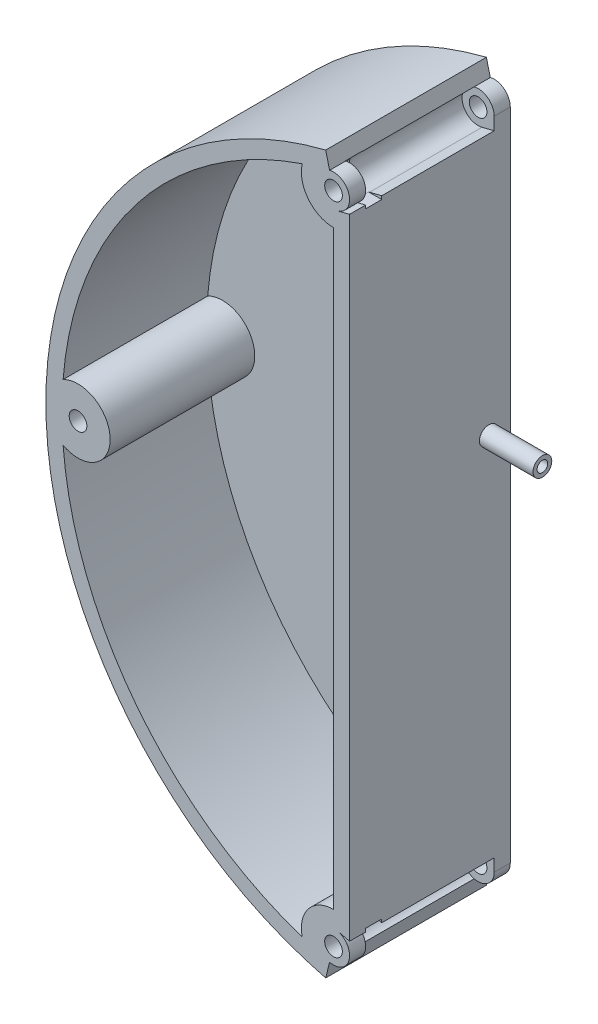
SolidWorks part; units mm, degrees
ref_plane "Front Plane" through (0, 0, 0) normal (0, 0, 1) x (1, 0, 0)
ref_plane "Top Plane" through (0, 0, 0) normal (0, 1, 0) x (1, 0, 0)
ref_plane "Right Plane" through (0, 0, 0) normal (1, 0, 0) x (0, 0, -1)
sketch "Sketch1" plane through (0, 0, 0) normal (0, 0, 1) x (1, 0, 0)
  line L0 (-12.3, -61.1139) -> (-12.3, 61.1139)
  line L1 (-12, -28.4) -> (-12, -52) construction
  line L2 (-16.7571, 66.9343) -> (-16.0286, 64.0241)
  line L4 (-16.7571, -66.9343) -> (-16.0286, -64.0241)
  line L5 (-63, 0) -> (0, 0) construction
  arc A1 (-16.0286, -64.0241) -> (-12.3, -61.1139) centre (-15.3, -61.1139) cw
  circle A2 centre (0, 0) radius 69 construction
  arc A3 (-16.0286, 64.0241) -> (-12.3, 61.1139) centre (-15.3, 61.1139) ccw
  circle A4 centre (-63, 0) radius 3
  arc A6 (-16.7571, 66.9343) -> (-16.7571, -66.9343) centre (0, 0) ccw
  dimension "D2" = 3
  dimension "D6" = 3
  dimension "D8" = 6
  dimension "D1" = 0.3
  dimension "D3" = 3
  dimension "D5" = 3
  dimension "D9" = 63
extrude "Boss-Extrude2" add sketch "Sketch1" along normal blind 30
shell "Shell1" thickness 3 removed face at (-24.7296, 0, 30)
sketch "Sketch3" plane through (-12.3, 0, 0) normal (1, 0, 0) x (0, 1, 0)
  line L0 (-61.1139, 0) -> (61.1139, 0) construction
  circle A0 centre (10, 4) radius 1.75
  dimension "D1" = 3.5
  dimension "D2" = 4
  dimension "D3" = 10
extrude "Boss-Extrude3" add sketch "Sketch3" along normal blind 10
sketch "Sketch5" plane through (0, 0, 0) normal (0, 0, 1) x (1, 0, 0)
  line L0 (-12.3, -61.1139) -> (-12.3, 61.1139)
  line L2 (-16.7571, 66.9343) -> (-16.0286, 64.0241)
  line L4 (-16.7571, -66.9343) -> (-16.0286, -64.0241)
  line L5 (-63, 0) -> (0, 0) construction
  circle A4 centre (-63, 0) radius 1.65
  circle A5 centre (-15.3, 61.1139) radius 1.65
  arc A6 (-16.7571, 66.9343) -> (-16.7571, -66.9343) centre (0, 0) ccw
  arc A7 (-16.0286, 64.0241) -> (-12.3, 61.1139) centre (-15.3, 61.1139) cw
  circle A8 centre (-15.3, -61.1139) radius 1.65
  arc A9 (-12.3, -61.1139) -> (-16.0286, -64.0241) centre (-15.3, -61.1139) cw
  dimension "D2" = 3.3
  dimension "D8" = 3.3
  dimension "D1" = 3.3
  dimension "D3" = 3
  dimension "D5" = 3
extrude "Boss-Extrude4" add sketch "Sketch5" along normal blind 3 contours A4 L0 A7 L2 A6 L4 A9 A8 A5 region at (-36.1775, 0, 0)
sketch "Sketch6" plane through (0, 0, 30) normal (0, 0, 1) x (1, 0, 0)
  line L0 (-63, 3) -> (-68.9348, 3)
  line L1 (-63, -3) -> (-68.9348, -3)
  line L2 (-16.0286, -64.0241) -> (-14.5714, -58.2037) construction
  line L3 (-14.5714, -58.2037) -> (-12.3, -58.7724)
  line L4 (-12.3, -61.1139) -> (-12.3, 61.1139) construction
  line L5 (-12.3, -58.7724) -> (-12.3, -61.1139)
  line L6 (-16.0286, 64.0241) -> (-14.5714, 58.2037) construction
  line L7 (-14.5714, 58.2037) -> (-12.3, 58.7724)
  line L8 (-12.3, 58.7724) -> (-12.3, 61.1139)
  arc A1 (-63, -3) -> (-63, 3) centre (-63, 0) ccw
  arc A2 (-12.3, -61.1139) -> (-14.5714, -58.2037) centre (-15.3, -61.1139) ccw
  arc A3 (-14.5714, 58.2037) -> (-12.3, 61.1139) centre (-15.3, 61.1139) ccw
  arc A4 (-16.7571, 66.9343) -> (-16.7571, -66.9343) centre (0, 0) ccw construction
  arc A5 (-68.9348, 3) -> (-68.9348, -3) centre (-68.9348, 0) ccw
  arc A6 (-12.3, -61.1139) -> (-16.0286, -64.0241) centre (-15.3, -61.1139) ccw construction
  arc A7 (-16.0286, 64.0241) -> (-12.3, 61.1139) centre (-15.3, 61.1139) ccw construction
extrude "Cut-Extrude1" cut sketch "Sketch6" against normal up to surface (27 mm away) up to face at (-61.35, 0, 3)
sketch "Sketch7" plane through (0, 0, 30) normal (0, 0, 1) x (1, 0, 0)
  line L0 (-13.5968, -58.1639) -> (-11.8936, -58.1639)
  line L1 (-11.8936, -61.1139) -> (-13.5968, -58.1639) construction
  line L2 (-13.5968, -58.1639) -> (-17.0032, -58.1639)
  line L3 (-17.0032, -58.1639) -> (-18.7064, -61.1139)
  line L4 (-18.7064, -61.1139) -> (-17.0032, -64.0639)
  line L5 (-17.0032, -64.0639) -> (-13.5968, -64.0639)
  line L6 (-13.5968, -64.0639) -> (-11.8936, -61.1139)
  line L7 (-11.8936, 61.1139) -> (-13.5968, 64.0639)
  line L8 (-13.5968, 64.0639) -> (-17.0032, 64.0639)
  line L9 (-17.0032, 64.0639) -> (-18.7064, 61.1139)
  line L10 (-18.7064, 61.1139) -> (-17.0032, 58.1639)
  line L11 (-17.0032, 58.1639) -> (-13.5968, 58.1639)
  line L12 (-13.5968, 58.1639) -> (-11.8936, 61.1139) construction
  line L13 (-59.5936, 0) -> (-61.2968, 2.95)
  line L14 (-61.2968, 2.95) -> (-64.7032, 2.95)
  line L15 (-64.7032, 2.95) -> (-66.4064, 0)
  line L16 (-66.4064, 0) -> (-64.7032, -2.95)
  line L17 (-64.7032, -2.95) -> (-61.2968, -2.95)
  line L18 (-61.2968, -2.95) -> (-59.5936, 0)
  line L19 (-11.8936, -58.1639) -> (-11.8936, -61.1139)
  line L20 (-13.5968, 58.1639) -> (-11.8936, 58.1639)
  line L21 (-11.8936, 58.1639) -> (-11.8936, 61.1139)
  circle A0 centre (-15.3, -61.1139) radius 2.95 construction
  circle A1 centre (-15.3, 61.1139) radius 2.95 construction
  circle A2 centre (-63, 0) radius 2.95 construction
  dimension "D1" = 5.9
  dimension "D2" = 5.9
  dimension "D3" = 5.9
extrude "Cut-Extrude2" cut sketch "Sketch7" against normal blind 3 from offset 3 offset against normal yes
sketch "Sketch8" plane through (0, 0, 30) normal (0, 0, 1) x (1, 0, 0)
  line L0 (-63, 3) -> (-68.9348, 3)
  line L1 (-68.9348, 3) -> (-68.9348, -3)
  line L2 (-68.9348, -3) -> (-63, -3) construction
  line L3 (-63, -3) -> (-68.9348, -3) construction
  line L4 (-68.9348, -3) -> (-63, -3)
  circle A0 centre (-63, 0) radius 1.65
  arc A1 (-63, -3) -> (-63, 3) centre (-63, 0) ccw
  circle A2 centre (-15.3, -61.1139) radius 1.65
  circle A3 centre (-15.3, -61.1139) radius 3
  circle A4 centre (-15.3, 61.1139) radius 1.65
  circle A5 centre (-15.3, 61.1139) radius 3
extrude "Boss-Extrude5" add sketch "Sketch8" against normal blind 3
sketch "Sketch9" plane through (-2.3, 0, 0) normal (1, 0, 0) x (0, 1, 0)
  circle A0 centre (10, 4) radius 1
  dimension "D1" = 2
extrude "Cut-Extrude3" cut sketch "Sketch9" against normal blind 30
